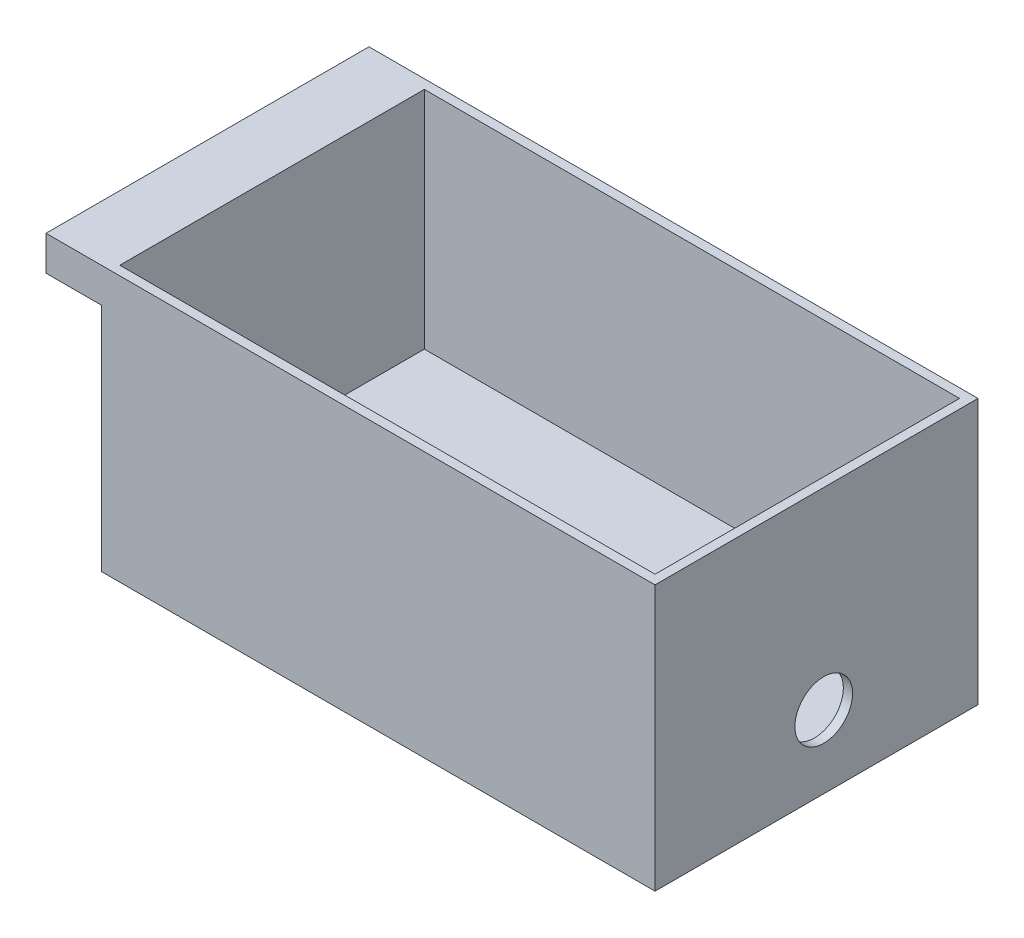
SolidWorks part; units mm, degrees
ref_plane "Front Plane" through (0, 0, 0) normal (0, 0, 1) x (1, 0, 0)
ref_plane "Top Plane" through (0, 0, 0) normal (0, 1, 0) x (1, 0, 0)
ref_plane "Right Plane" through (0, 0, 0) normal (1, 0, 0) x (0, 0, -1)
sketch "Sketch1" plane through (0, 0, 0) normal (0, 1, 0) x (1, 0, 0)
  line L1 (-10.4, 5.9429) -> (13.6, 5.9429)
  line L2 (-10.4, 5.9429) -> (-10.4, -8.0571)
  line L3 (-10.4, -8.0571) -> (13.6, -8.0571)
  line L4 (13.6, 5.9429) -> (13.6, -8.0571)
  dimension "D1" = 24
  dimension "D2" = 14
extrude "Boss-Extrude1" add sketch "Sketch1" along normal blind 11.5
sketch "Sketch2" plane through (0, 11.5, 0) normal (0, 1, 0) x (1, 0, 0)
  line L0 (13.6, 5.9429) -> (-10.4, 5.9429) construction
  line L1 (-10, 5.5429) -> (13.2, 5.5429)
  line L2 (-10, 5.5429) -> (-10, -7.6571)
  line L3 (-10, -7.6571) -> (13.2, -7.6571)
  line L4 (13.2, 5.5429) -> (13.2, -7.6571)
  line L5 (-10.4, 5.9429) -> (-10.4, -8.0571) construction
  dimension "D1" = 23.2
  dimension "D2" = 13.2
  dimension "D3" = 0.4
  dimension "D4" = 0.4
extrude "Cut-Extrude1" cut sketch "Sketch2" against normal blind 9.75
sketch "Sketch3" plane through (13.6, 0, 0) normal (1, 0, 0) x (0, 0, -1)
  circle A0 centre (-0.7438, 3.1471) radius 1.25
  dimension "D1" = 2.5
extrude "Cut-Extrude2" cut sketch "Sketch3" against normal blind 3
sketch "Sketch5" plane through (0, 11.5, 0) normal (0, 1, 0) x (1, 0, 0)
  line L1 (-10.4, 5.9429) -> (-12.8, 5.9429)
  line L2 (-10.4, 5.9429) -> (-10.4, -8.0571)
  line L3 (-10.4, -8.0571) -> (-12.8, -8.0571)
  line L4 (-12.8, 5.9429) -> (-12.8, -8.0571)
  point P5 (-10.4, 5.9429)
  dimension "D1" = 2.4
extrude "Boss-Extrude2" add sketch "Sketch5" against normal blind 1.5
sketch "Sketch7" plane through (0, 1.75, 0) normal (0, 1, 0) x (1, 0, 0)
  line L0 (1.6, 5.5429) -> (1.6, 12.512) construction
  line L1 (13.2, 5.5429) -> (-10, 5.5429) construction
